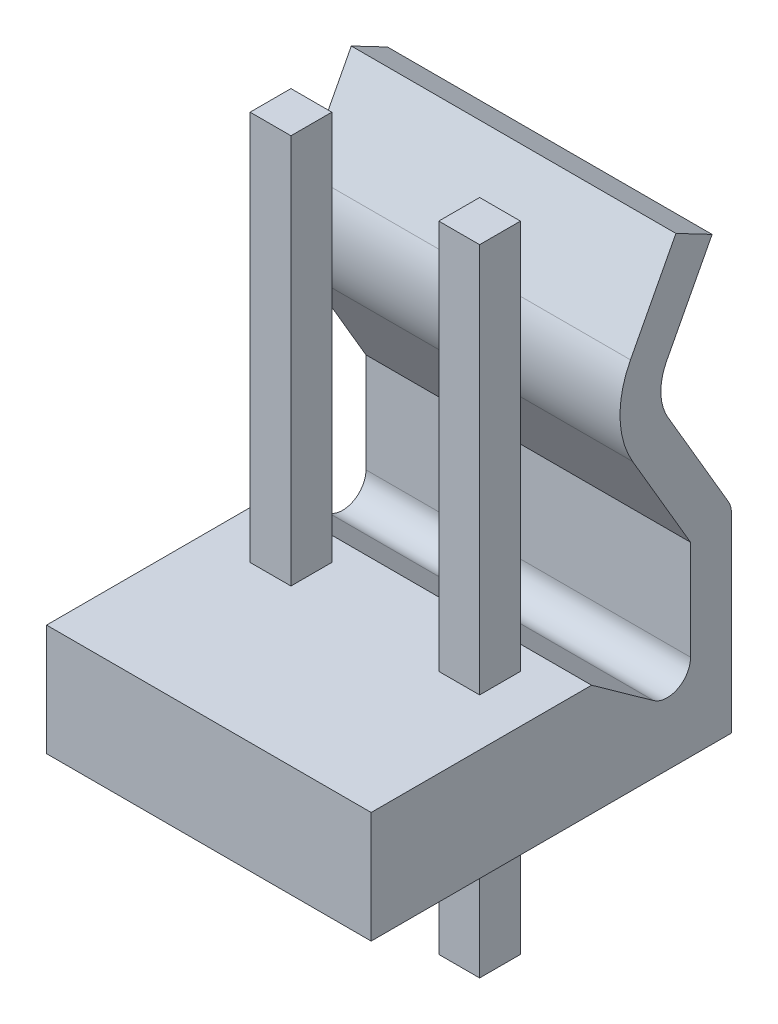
SolidWorks part; units mm, degrees
ref_plane "Alzado" through (0, 0, 0) normal (0, 0, 1) x (1, 0, 0)
ref_plane "Planta" through (0, 0, 0) normal (0, 1, 0) x (1, 0, 0)
ref_plane "Vista lateral" through (0, 0, 0) normal (1, 0, 0) x (0, 0, -1)
sketch "Croquis1" plane through (0, 0, 0) normal (0, 1, 0) x (1, 0, 0)
  line L0 (-1.83, 4.95) -> (6.91, 4.95)
  line L1 (6.91, 4.95) -> (6.91, -4.75)
  line L2 (6.91, -4.75) -> (-1.83, -4.75)
  line L3 (-1.83, -4.75) -> (-1.83, 4.95)
  line L4 (2.54, -4.75) -> (2.54, 2.1284) construction
  line L5 (-0.55, -0.55) -> (0.55, -0.55)
  line L6 (-0.55, -0.55) -> (-0.55, 0.55)
  line L7 (-0.55, 0.55) -> (0.55, 0.55)
  line L8 (0.55, -0.55) -> (0.55, 0.55)
  line L9 (-0.55, -0.55) -> (0.55, 0.55) construction
  line L10 (-0.55, 0.55) -> (0.55, -0.55) construction
  line L11 (5.63, -0.55) -> (5.63, 0.55)
  line L12 (5.63, -0.55) -> (4.53, -0.55)
  line L13 (4.53, -0.55) -> (4.53, 0.55)
  line L14 (5.63, 0.55) -> (4.53, 0.55)
  point P5 (0, 0)
  point P16 (0, -0.55)
  point P17 (5.08, -0.55)
  dimension "D1" = 8.74
  dimension "D2" = 9.7
  dimension "D3" = 4.75
  dimension "D4" = 5.08
  dimension "D5" = 1.1
  dimension "D6" = 1.1
extrude "Saliente-Extruir1" add sketch "Croquis1" along normal blind 3
sketch "Croquis2" plane through (0, 3, 0) normal (0, 1, 0) x (1, 0, 0)
  line L0 (-1.83, 4.95) -> (-1.83, -4.75) construction
  line L3 (-1.83, 1.95) -> (6.91, 1.95)
  line L4 (-1.83, 4.95) -> (-1.83, -4.75)
  line L5 (-1.83, -4.75) -> (6.91, -4.75)
  line L6 (6.91, -4.75) -> (6.91, 4.95)
  line L7 (6.91, 4.95) -> (-1.83, 4.95)
  line L11 (6.91, 4.95) -> (-1.83, 4.95)
  line L13 (6.91, -4.75) -> (6.91, 4.95) construction
  point P2 (2.54, 0.1)
  line M13 (-1.83, 4.95) -> (-1.83, -4.75)
  line M15 (6.91, -4.75) -> (6.91, 4.95)
  line M16 (6.91, 4.95) -> (-1.83, 4.95)
  dimension "D2" = 3
  dimension "D1" = 0
extrude "Saliente-Extruir2" add sketch "Croquis2" along normal blind 9.4 contours L3 M13 M15 M16 region at (2.54, 3, -3.45)
sketch "Croquis3" plane through (-1.83, 0, 0) normal (-1, 0, 0) x (0, 0, 1)
  line L1 (-4.95, 5.1309) -> (-4.95, 12.4)
  line L7 (-3.85, 2.32) -> (-3.85, 5)
  line L8 (-3.85, 5) -> (-2.2894, 7.6645)
  line L12 (-4.95, 12.4) -> (-1.95, 12.4) construction
  line L13 (-3.45, 12.4) -> (-1.95, 12.4)
  line L14 (-1.95, 12.4) -> (-1.95, 3)
  line L15 (-1.1844, 3) -> (-2.8543, 1.8075)
  line L16 (-1.95, 3) -> (4.75, 3) construction
  line L17 (-1.95, 3) -> (-1.1844, 3)
  line L18 (-4.95, 12.4) -> (-4.95, 0) construction
  line L19 (-3.4553, 12.4) -> (-2.2323, 10.0635)
  line L20 (-3.4553, 12.4) -> (-4.4299, 11.8899)
  line L21 (-4.4299, 11.8899) -> (-3.2068, 9.5533)
  line L22 (-3.2386, 8.2204) -> (-4.8653, 5.443)
  arc A2 (-3.85, 2.32) -> (-2.8543, 1.8075) centre (-3.2203, 2.32) ccw
  arc A4 (-3.2386, 8.2204) -> (-3.2068, 9.5533) centre (-4.4254, 8.9155) ccw
  arc A5 (-4.8653, 5.443) -> (-4.95, 5.1309) centre (-4.3326, 5.1309) ccw
  arc A6 (-2.2894, 7.6645) -> (-2.2323, 10.0635) centre (-4.4254, 8.9155) ccw
  line M9 (-4.95, 12.4) -> (-4.95, 0)
  line M11 (-1.95, 3) -> (-1.95, 12.4)
  line M12 (-1.95, 12.4) -> (-4.95, 12.4)
  dimension "D1" = 1.1
  dimension "D2" = 2
  dimension "D3" = 1.1
extrude "Cortar-Extruir1" cut sketch "Croquis3" against normal blind 9 contours L8 L7 M11 | M11 M12 | A5 L22 A4 L21 L20 M12 M9 region at (-1.83, 4.3559, -2.7805) region at (-1.83, 11.4156, -2.4458) region at (-1.83, 9.119, -4.2584)
sketch "Croquis5" plane through (0, 0, 0) normal (0, 1, 0) x (1, 0, 0)
  line L0 (5.63, -0.55) -> (5.63, 0.55) construction
  line L1 (4.53, -0.55) -> (5.63, -0.55) construction
  line L2 (4.53, 0.55) -> (4.53, -0.55) construction
  line L3 (5.63, 0.55) -> (4.53, 0.55) construction
  line L4 (0.55, 0.55) -> (-0.55, 0.55) construction
  line L5 (0.55, -0.55) -> (0.55, 0.55) construction
  line L6 (-0.55, -0.55) -> (0.55, -0.55) construction
  line L7 (-0.55, 0.55) -> (-0.55, -0.55) construction
  line L8 (5.63, -0.55) -> (5.63, 0.55)
  line L9 (4.53, -0.55) -> (5.63, -0.55)
  line L10 (4.53, 0.55) -> (4.53, -0.55)
  line L11 (5.63, 0.55) -> (4.53, 0.55)
  line L12 (0.55, 0.55) -> (-0.55, 0.55)
  line L13 (0.55, -0.55) -> (0.55, 0.55)
  line L14 (-0.55, -0.55) -> (0.55, -0.55)
  line L15 (-0.55, 0.55) -> (-0.55, -0.55)
extrude "Saliente-Extruir3" add sketch "Croquis5" along normal blind 13.5 and the other way blind 3.6
